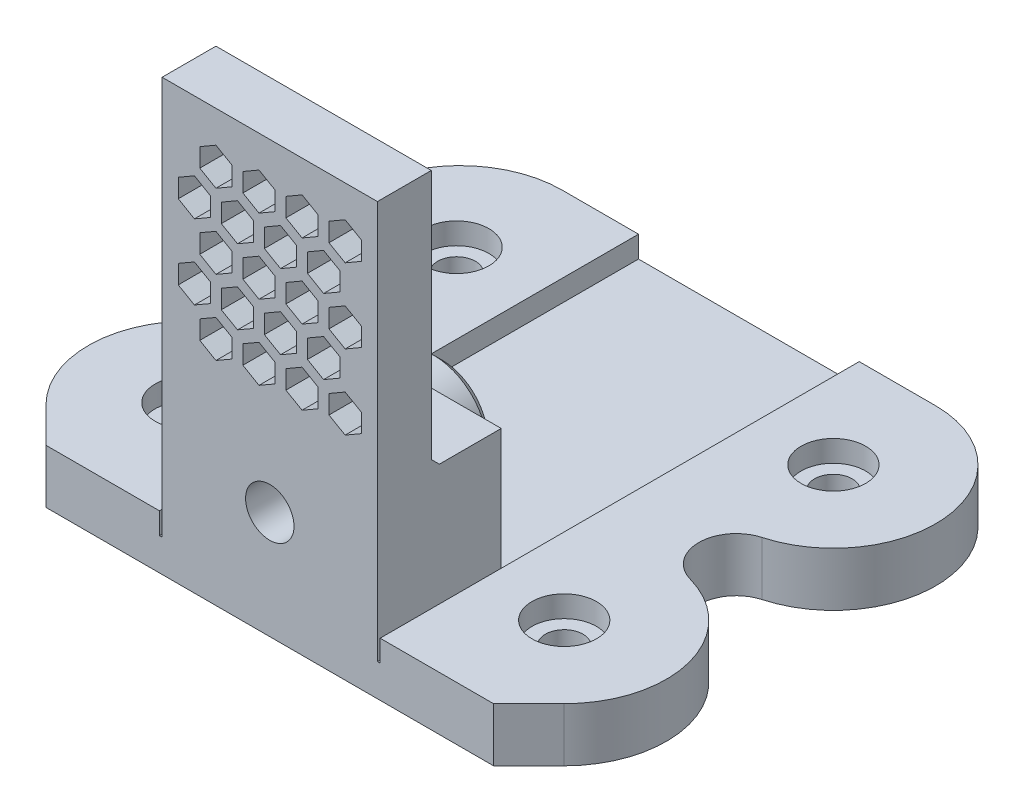
SolidWorks part; units mm, degrees
ref_plane "Front Plane" through (0, 0, 0) normal (0, 0, 1) x (1, 0, 0)
ref_plane "Top Plane" through (0, 0, 0) normal (0, 1, 0) x (1, 0, 0)
ref_plane "Right Plane" through (0, 0, 0) normal (1, 0, 0) x (0, 0, -1)
sketch "Sketch1" plane through (0, 0, 0) normal (1, 0, 0) x (0, 0, -1)
  line L0 (0, 0) -> (0, 40)
  line L1 (0, 40) -> (5, 40)
  line L2 (5, 40) -> (5, 16.75)
  line L3 (5, 16.75) -> (5.75, 16)
  line L4 (5.75, 16) -> (11.5, 16)
  line L5 (11.5, 16) -> (11.5, 3)
  line L6 (11.5, 3) -> (44.5, 3)
  line L7 (44.5, 3) -> (44.5, 0)
  line L8 (44.5, 0) -> (0, 0)
  line L9 (11.5, 3) -> (44, 3) construction
  line L10 (11.5, 16) -> (11.5, 3) construction
  line L11 (7, 16) -> (11.5, 16) construction
  dimension "D1" = 40
  dimension "D2" = 6.5
  dimension "D3" = 135
  dimension "D4" = 0.75
  dimension "D5" = 33
extrude "Boss-Extrude1" add sketch "Sketch1" against normal blind 20
sketch "Sketch2" plane through (0, 0, -11.5) normal (0, 0, -1) x (-1, 0, 0)
  circle A0 centre (10, 10) radius 2 construction
  circle A1 centre (10, 10) radius 5.25 construction
  circle A2 centre (10, 10) radius 5
  circle A3 centre (10, 10) radius 2.25
  circle A4 centre (10, 10) radius 2.75 construction
  dimension "D3" = 4
  dimension "D4" = 10
  dimension "D1" = 0.25
  dimension "D2" = 0.25
extrude "Boss-Extrude2" add sketch "Sketch2" along normal blind 4.5
chamfer "Chamfer1" distance 0.75 angle 45 1 edges at (-10, 15, -16)
extrude "Cut-Extrude1" cut sketch "Sketch2<2>" against normal up to next contours A3 region at (-10, 10, -11.5)
sketch "Sketch2<2>" plane through (0, 0, -11.5) normal (0, 0, -1) x (-1, 0, 0) same geometry as "Sketch2"
sketch "Sketch3" plane through (0, 3, 0) normal (0, 1, 0) x (1, 0, 0)
  line L0 (0, 44.5) -> (7.35, 44.5)
  line L1 (-10, 44.5) -> (-10, 11.5) construction
  line L2 (-20, 44.5) -> (0, 44.5) construction
  line L3 (-20, 11.5) -> (0, 11.5) construction
  line L4 (7.35, 44.5) -> (7.35, 0.5) construction
  line L5 (14.0675, 3.2825) -> (10.785, 0)
  line L6 (10.785, 0) -> (0, 0)
  line L7 (0, 0) -> (0, 11.5)
  line L8 (0, 11.5) -> (-20, 11.5)
  line L9 (0, 44.5) -> (-20, 44.5)
  line L10 (-20, 0) -> (-20, 11.5)
  line L11 (-30.785, 0) -> (-20, 0)
  line L12 (-34.0675, 3.2825) -> (-30.785, 0)
  line L13 (-20, 44.5) -> (-27.35, 44.5)
  arc A0 (7.35, 44.5) -> (9.8936, 25.8469) centre (7.35, 35) cw
  arc A1 (9.8936, 25.8469) -> (9.8936, 19.1531) centre (10.8237, 22.5) ccw
  arc A2 (9.8936, 19.1531) -> (14.0675, 3.2825) centre (7.35, 10) cw
  circle A3 centre (7.35, 35) radius 1.75 construction
  circle A4 centre (7.35, 10) radius 1.75
  circle A5 centre (7.35, 10) radius 1.75 construction
  arc A6 (14.0675, 3.2825) -> (7.35, 0.5) centre (7.35, 10) cw construction
  circle A7 centre (7.35, 35) radius 1.75
  arc A10 (-29.8936, 19.1531) -> (-34.0675, 3.2825) centre (-27.35, 10) ccw
  arc A11 (-29.8936, 25.8469) -> (-29.8936, 19.1531) centre (-30.8237, 22.5) cw
  arc A12 (-27.35, 44.5) -> (-29.8936, 25.8469) centre (-27.35, 35) ccw
  circle A14 centre (-27.65, 10) radius 1.75
  circle A15 centre (-27.65, 35) radius 1.75
  circle A16 centre (-27.65, 35) radius 1.75 construction
  circle A17 centre (-27.65, 10) radius 1.75 construction
  point P22 (7.35, 22.5)
  point P37 (-27.35, 22.5)
  dimension "D2" = 3.5
  dimension "D1" = 135
extrude "Boss-Extrude3" add sketch "Sketch3" against normal up to surface (3 mm away) up to face at (-10, 0, -22.25)
sketch "Sketch4" plane through (0, 3, 0) normal (0, 1, 0) x (1, 0, 0)
  line L0 (-30.785, 0) -> (-20, 0) construction
  line L1 (-34.0675, 3.2825) -> (-30.785, 0) construction
  line L2 (-27.35, 44.5) -> (7.35, 44.5) construction
  line L3 (10.785, 0) -> (14.0675, 3.2825) construction
  line L5 (-30.785, 0) -> (-20.25, 0)
  line L6 (-34.0675, 3.2825) -> (-30.785, 0)
  line L7 (-27.35, 44.5) -> (-20.25, 44.5)
  line L8 (10.785, 0) -> (14.0675, 3.2825)
  line L10 (-20, 0) -> (-20, 11.5) construction
  line L11 (0, 11.5) -> (0, 0) construction
  line L20 (-20, 0) -> (-20, 11.5) construction
  line L21 (0, 11.5) -> (0, 0) construction
  line L22 (0.25, 44.5) -> (0.25, 0)
  line L23 (0.25, 11.5) -> (0.25, 0) construction
  line L24 (-20.25, 0) -> (-20.25, 44.5)
  line L25 (-20.25, 0) -> (-20.25, 11.5) construction
  line L26 (0.25, 44.5) -> (7.35, 44.5)
  line L27 (-20.25, 44.5) -> (0.25, 44.5) construction
  line L28 (0.25, 0) -> (10.785, 0)
  arc A0 (-29.8936, 19.1531) -> (-34.0675, 3.2825) centre (-27.35, 10) ccw construction
  arc A1 (-29.8936, 19.1531) -> (-29.8936, 25.8469) centre (-30.8237, 22.5) ccw construction
  arc A2 (-27.35, 44.5) -> (-29.8936, 25.8469) centre (-27.35, 35) ccw construction
  arc A3 (9.8936, 25.8469) -> (7.35, 44.5) centre (7.35, 35) ccw construction
  arc A4 (9.8936, 25.8469) -> (9.8936, 19.1531) centre (10.8237, 22.5) ccw construction
  arc A5 (14.0675, 3.2825) -> (9.8936, 19.1531) centre (7.35, 10) ccw construction
  arc A6 (-29.8936, 19.1531) -> (-34.0675, 3.2825) centre (-27.35, 10) ccw
  arc A7 (-29.8936, 19.1531) -> (-29.8936, 25.8469) centre (-30.8237, 22.5) ccw
  arc A8 (-27.35, 44.5) -> (-29.8936, 25.8469) centre (-27.35, 35) ccw
  arc A9 (9.8936, 25.8469) -> (7.35, 44.5) centre (7.35, 35) ccw
  arc A10 (9.8936, 25.8469) -> (9.8936, 19.1531) centre (10.8237, 22.5) ccw
  arc A11 (14.0675, 3.2825) -> (9.8936, 19.1531) centre (7.35, 10) ccw
  circle A12 centre (7.35, 10) radius 2.75 construction
  circle A13 centre (7.35, 35) radius 3
  circle A16 centre (7.35, 10) radius 3
  circle A19 centre (-27.65, 10) radius 3
  circle A20 centre (-27.65, 35) radius 3
  circle A21 centre (-27.65, 35) radius 1.75 construction
  circle A22 centre (-27.65, 10) radius 1.75 construction
  dimension "D1" = 0.25
  dimension "D2" = 0.25
  dimension "D4" = 5.5
  dimension "D3" = 0.25
extrude "Boss-Extrude4" add sketch "Sketch4" along normal blind 2
sketch "Sketch5" plane through (0, 0, -5) normal (0, 0, -1) x (-1, 0, 0)
  line L0 (1.5, 37.0353) -> (0, 37.0353) construction
  line L1 (3, 19.7147) -> (4.5, 20.5808)
  line L2 (4.5, 20.5808) -> (4.5, 22.3128)
  line L3 (4.5, 22.3128) -> (3, 23.1788)
  line L4 (3, 23.1788) -> (1.5, 22.3128)
  line L5 (1.5, 22.3128) -> (1.5, 20.5808)
  line L6 (1.5, 20.5808) -> (3, 19.7147)
  line L7 (1.5, 19.7147) -> (18.5, 19.7147) construction
  line L8 (1.5, 19.7147) -> (1.5, 37.0353) construction
  line L9 (1.5, 37.0353) -> (18.5, 37.0353) construction
  line L10 (18.5, 19.7147) -> (18.5, 37.0353) construction
  line L11 (0, 16.75) -> (0, 40) construction
  line L12 (1.5, 40) -> (1.5, 37.0353) construction
  line L13 (20, 40) -> (0, 40) construction
  line L14 (20, 19.7147) -> (18.5, 19.7147) construction
  line L15 (20, 16.75) -> (20, 40) construction
  line L16 (18.5, 19.7147) -> (18.5, 16.75) construction
  line L17 (20, 16.75) -> (0, 16.75) construction
  line L18 (7, 19.7147) -> (8.5, 20.5808)
  line L19 (8.5, 20.5808) -> (8.5, 22.3128)
  line L20 (8.5, 22.3128) -> (7, 23.1788)
  line L21 (7, 23.1788) -> (5.5, 22.3128)
  line L22 (5.5, 22.3128) -> (5.5, 20.5808)
  line L23 (5.5, 20.5808) -> (7, 19.7147)
  line L24 (11, 19.7147) -> (12.5, 20.5808)
  line L25 (12.5, 20.5808) -> (12.5, 22.3128)
  line L26 (12.5, 22.3128) -> (11, 23.1788)
  line L27 (11, 23.1788) -> (9.5, 22.3128)
  line L28 (9.5, 22.3128) -> (9.5, 20.5808)
  line L29 (9.5, 20.5808) -> (11, 19.7147)
  line L30 (15, 19.7147) -> (16.5, 20.5808)
  line L31 (16.5, 20.5808) -> (16.5, 22.3128)
  line L32 (16.5, 22.3128) -> (15, 23.1788)
  line L33 (15, 23.1788) -> (13.5, 22.3128)
  line L34 (13.5, 22.3128) -> (13.5, 20.5808)
  line L35 (13.5, 20.5808) -> (15, 19.7147)
  line L36 (19, 19.7147) -> (20.5, 20.5808) construction
  line L37 (20.5, 20.5808) -> (20.5, 22.3128) construction
  line L38 (20.5, 22.3128) -> (19, 23.1788) construction
  line L39 (19, 23.1788) -> (17.5, 22.3128) construction
  line L40 (17.5, 22.3128) -> (17.5, 20.5808) construction
  line L41 (17.5, 20.5808) -> (19, 19.7147) construction
  line L42 (23, 19.7147) -> (24.5, 20.5808) construction
  line L43 (24.5, 20.5808) -> (24.5, 22.3128) construction
  line L44 (24.5, 22.3128) -> (23, 23.1788) construction
  line L45 (23, 23.1788) -> (21.5, 22.3128) construction
  line L46 (21.5, 22.3128) -> (21.5, 20.5808) construction
  line L47 (21.5, 20.5808) -> (23, 19.7147) construction
  line L60 (3, 21.4468) -> (-6, 37.0353) construction
  line L61 (-6, 37.0353) -> (0, 37.0353) construction
  line L68 (5, 23.1788) -> (6.5, 24.0449)
  line L69 (6.5, 24.0449) -> (6.5, 25.7769)
  line L70 (6.5, 25.7769) -> (5, 26.6429)
  line L71 (5, 26.6429) -> (3.5, 25.7769)
  line L72 (3.5, 25.7769) -> (3.5, 24.0449)
  line L73 (3.5, 24.0449) -> (5, 23.1788)
  line L74 (9, 23.1788) -> (10.5, 24.0449)
  line L75 (10.5, 24.0449) -> (10.5, 25.7769)
  line L76 (10.5, 25.7769) -> (9, 26.6429)
  line L77 (9, 26.6429) -> (7.5, 25.7769)
  line L78 (7.5, 25.7769) -> (7.5, 24.0449)
  line L79 (7.5, 24.0449) -> (9, 23.1788)
  line L80 (13, 23.1788) -> (14.5, 24.0449)
  line L81 (14.5, 24.0449) -> (14.5, 25.7769)
  line L82 (14.5, 25.7769) -> (13, 26.6429)
  line L83 (13, 26.6429) -> (11.5, 25.7769)
  line L84 (11.5, 25.7769) -> (11.5, 24.0449)
  line L85 (11.5, 24.0449) -> (13, 23.1788)
  line L86 (17, 23.1788) -> (18.5, 24.0449)
  line L87 (18.5, 24.0449) -> (18.5, 25.7769)
  line L88 (18.5, 25.7769) -> (17, 26.6429)
  line L89 (17, 26.6429) -> (15.5, 25.7769)
  line L90 (15.5, 25.7769) -> (15.5, 24.0449)
  line L91 (15.5, 24.0449) -> (17, 23.1788)
  line L116 (3, 26.6429) -> (4.5, 27.509)
  line L117 (4.5, 27.509) -> (4.5, 29.241)
  line L118 (4.5, 29.241) -> (3, 30.1071)
  line L119 (3, 30.1071) -> (1.5, 29.241)
  line L120 (1.5, 29.241) -> (1.5, 27.509)
  line L121 (1.5, 27.509) -> (3, 26.6429)
  line L122 (7, 26.6429) -> (8.5, 27.509)
  line L123 (8.5, 27.509) -> (8.5, 29.241)
  line L124 (8.5, 29.241) -> (7, 30.1071)
  line L125 (7, 30.1071) -> (5.5, 29.241)
  line L126 (5.5, 29.241) -> (5.5, 27.509)
  line L127 (5.5, 27.509) -> (7, 26.6429)
  line L128 (11, 26.6429) -> (12.5, 27.509)
  line L129 (12.5, 27.509) -> (12.5, 29.241)
  line L130 (12.5, 29.241) -> (11, 30.1071)
  line L131 (11, 30.1071) -> (9.5, 29.241)
  line L132 (9.5, 29.241) -> (9.5, 27.509)
  line L133 (9.5, 27.509) -> (11, 26.6429)
  line L134 (15, 26.6429) -> (16.5, 27.509)
  line L135 (16.5, 27.509) -> (16.5, 29.241)
  line L136 (16.5, 29.241) -> (15, 30.1071)
  line L137 (15, 30.1071) -> (13.5, 29.241)
  line L138 (13.5, 29.241) -> (13.5, 27.509)
  line L139 (13.5, 27.509) -> (15, 26.6429)
  line L170 (5, 30.1071) -> (6.5, 30.9731)
  line L171 (6.5, 30.9731) -> (6.5, 32.7051)
  line L172 (6.5, 32.7051) -> (5, 33.5712)
  line L173 (5, 33.5712) -> (3.5, 32.7051)
  line L174 (3.5, 32.7051) -> (3.5, 30.9731)
  line L175 (3.5, 30.9731) -> (5, 30.1071)
  line L176 (9, 30.1071) -> (10.5, 30.9731)
  line L177 (10.5, 30.9731) -> (10.5, 32.7051)
  line L178 (10.5, 32.7051) -> (9, 33.5712)
  line L179 (9, 33.5712) -> (7.5, 32.7051)
  line L180 (7.5, 32.7051) -> (7.5, 30.9731)
  line L181 (7.5, 30.9731) -> (9, 30.1071)
  line L182 (13, 30.1071) -> (14.5, 30.9731)
  line L183 (14.5, 30.9731) -> (14.5, 32.7051)
  line L184 (14.5, 32.7051) -> (13, 33.5712)
  line L185 (13, 33.5712) -> (11.5, 32.7051)
  line L186 (11.5, 32.7051) -> (11.5, 30.9731)
  line L187 (11.5, 30.9731) -> (13, 30.1071)
  line L188 (17, 30.1071) -> (18.5, 30.9731)
  line L189 (18.5, 30.9731) -> (18.5, 32.7051)
  line L190 (18.5, 32.7051) -> (17, 33.5712)
  line L191 (17, 33.5712) -> (15.5, 32.7051)
  line L192 (15.5, 32.7051) -> (15.5, 30.9731)
  line L193 (15.5, 30.9731) -> (17, 30.1071)
  line L218 (3, 33.5712) -> (4.5, 34.4372)
  line L219 (4.5, 34.4372) -> (4.5, 36.1692)
  line L220 (4.5, 36.1692) -> (3, 37.0353)
  line L221 (3, 37.0353) -> (1.5, 36.1692)
  line L222 (1.5, 36.1692) -> (1.5, 34.4372)
  line L223 (1.5, 34.4372) -> (3, 33.5712)
  line L224 (7, 33.5712) -> (8.5, 34.4372)
  line L225 (8.5, 34.4372) -> (8.5, 36.1692)
  line L226 (8.5, 36.1692) -> (7, 37.0353)
  line L227 (7, 37.0353) -> (5.5, 36.1692)
  line L228 (5.5, 36.1692) -> (5.5, 34.4372)
  line L229 (5.5, 34.4372) -> (7, 33.5712)
  line L230 (11, 33.5712) -> (12.5, 34.4372)
  line L231 (12.5, 34.4372) -> (12.5, 36.1692)
  line L232 (12.5, 36.1692) -> (11, 37.0353)
  line L233 (11, 37.0353) -> (9.5, 36.1692)
  line L234 (9.5, 36.1692) -> (9.5, 34.4372)
  line L235 (9.5, 34.4372) -> (11, 33.5712)
  line L236 (15, 33.5712) -> (16.5, 34.4372)
  line L237 (16.5, 34.4372) -> (16.5, 36.1692)
  line L238 (16.5, 36.1692) -> (15, 37.0353)
  line L239 (15, 37.0353) -> (13.5, 36.1692)
  line L240 (13.5, 36.1692) -> (13.5, 34.4372)
  line L241 (13.5, 34.4372) -> (15, 33.5712)
  line L302 (1, 23.1788) -> (2.5, 24.0449) [skipped]
  line L303 (2.5, 24.0449) -> (2.5, 25.7769) [skipped]
  line L304 (2.5, 25.7769) -> (1, 26.6429) [skipped]
  line L305 (1, 26.6429) -> (-0.5, 25.7769) [skipped]
  line L306 (-0.5, 25.7769) -> (-0.5, 24.0449) [skipped]
  line L307 (-0.5, 24.0449) -> (1, 23.1788) [skipped]
  line L308 (1, 30.1071) -> (2.5, 30.9731) [skipped]
  line L309 (2.5, 30.9731) -> (2.5, 32.7051) [skipped]
  line L310 (2.5, 32.7051) -> (1, 33.5712) [skipped]
  line L311 (1, 33.5712) -> (-0.5, 32.7051) [skipped]
  line L312 (-0.5, 32.7051) -> (-0.5, 30.9731) [skipped]
  line L313 (-0.5, 30.9731) -> (1, 30.1071) [skipped]
  line L314 (1, 37.0353) -> (2.5, 37.9013) [skipped]
  line L315 (2.5, 37.9013) -> (2.5, 39.6333) [skipped]
  line L316 (2.5, 39.6333) -> (1, 40.4994) [skipped]
  line L317 (1, 40.4994) -> (-0.5, 39.6333) [skipped]
  line L318 (-0.5, 39.6333) -> (-0.5, 37.9013) [skipped]
  line L319 (-0.5, 37.9013) -> (1, 37.0353) [skipped]
  line L320 (-1, 33.5712) -> (0.5, 34.4372) [skipped]
  line L321 (0.5, 34.4372) -> (0.5, 36.1692) [skipped]
  line L322 (0.5, 36.1692) -> (-1, 37.0353) [skipped]
  line L323 (-1, 37.0353) -> (-2.5, 36.1692) [skipped]
  line L324 (-2.5, 36.1692) -> (-2.5, 34.4372) [skipped]
  line L325 (-2.5, 34.4372) -> (-1, 33.5712) [skipped]
  line L326 (-3, 37.0353) -> (-1.5, 37.9013) [skipped]
  line L327 (-1.5, 37.9013) -> (-1.5, 39.6333) [skipped]
  line L328 (-1.5, 39.6333) -> (-3, 40.4994) [skipped]
  line L329 (-3, 40.4994) -> (-4.5, 39.6333) [skipped]
  line L330 (-4.5, 39.6333) -> (-4.5, 37.9013) [skipped]
  line L331 (-4.5, 37.9013) -> (-3, 37.0353) [skipped]
  line L332 (-7, 37.0353) -> (-5.5, 37.9013) [skipped]
  line L333 (-5.5, 37.9013) -> (-5.5, 39.6333) [skipped]
  line L334 (-5.5, 39.6333) -> (-7, 40.4994) [skipped]
  line L335 (-7, 40.4994) -> (-8.5, 39.6333) [skipped]
  line L336 (-8.5, 39.6333) -> (-8.5, 37.9013) [skipped]
  line L337 (-8.5, 37.9013) -> (-7, 37.0353) [skipped]
  line L338 (-5, 33.5712) -> (-3.5, 34.4372) [skipped]
  line L339 (-3.5, 34.4372) -> (-3.5, 36.1692) [skipped]
  line L340 (-3.5, 36.1692) -> (-5, 37.0353) [skipped]
  line L341 (-5, 37.0353) -> (-6.5, 36.1692) [skipped]
  line L342 (-6.5, 36.1692) -> (-6.5, 34.4372) [skipped]
  line L343 (-6.5, 34.4372) -> (-5, 33.5712) [skipped]
  line L344 (-3, 30.1071) -> (-1.5, 30.9731) [skipped]
  line L345 (-1.5, 30.9731) -> (-1.5, 32.7051) [skipped]
  line L346 (-1.5, 32.7051) -> (-3, 33.5712) [skipped]
  line L347 (-3, 33.5712) -> (-4.5, 32.7051) [skipped]
  line L348 (-4.5, 32.7051) -> (-4.5, 30.9731) [skipped]
  line L349 (-4.5, 30.9731) -> (-3, 30.1071) [skipped]
  line L350 (-1, 26.6429) -> (0.5, 27.509) [skipped]
  line L351 (0.5, 27.509) -> (0.5, 29.241) [skipped]
  line L352 (0.5, 29.241) -> (-1, 30.1071) [skipped]
  line L353 (-1, 30.1071) -> (-2.5, 29.241) [skipped]
  line L354 (-2.5, 29.241) -> (-2.5, 27.509) [skipped]
  line L355 (-2.5, 27.509) -> (-1, 26.6429) [skipped]
  line L356 (31, 19.7147) -> (32.5, 20.5808) [skipped]
  line L357 (32.5, 20.5808) -> (32.5, 22.3128) [skipped]
  line L358 (32.5, 22.3128) -> (31, 23.1788) [skipped]
  line L359 (31, 23.1788) -> (29.5, 22.3128) [skipped]
  line L360 (29.5, 22.3128) -> (29.5, 20.5808) [skipped]
  line L361 (29.5, 20.5808) -> (31, 19.7147) [skipped]
  line L380 (19, 26.6429) -> (20.5, 27.509) [skipped]
  line L381 (20.5, 27.509) -> (20.5, 29.241) [skipped]
  line L382 (20.5, 29.241) -> (19, 30.1071) [skipped]
  line L383 (19, 30.1071) -> (17.5, 29.241) [skipped]
  line L384 (17.5, 29.241) -> (17.5, 27.509) [skipped]
  line L385 (17.5, 27.509) -> (19, 26.6429) [skipped]
  line L386 (21, 23.1788) -> (22.5, 24.0449) [skipped]
  line L387 (22.5, 24.0449) -> (22.5, 25.7769) [skipped]
  line L388 (22.5, 25.7769) -> (21, 26.6429) [skipped]
  line L389 (21, 26.6429) -> (19.5, 25.7769) [skipped]
  line L390 (19.5, 25.7769) -> (19.5, 24.0449) [skipped]
  line L391 (19.5, 24.0449) -> (21, 23.1788) [skipped]
  line L404 (13, 37.0353) -> (14.5, 37.9013) [skipped]
  line L405 (14.5, 37.9013) -> (14.5, 39.6333) [skipped]
  line L406 (14.5, 39.6333) -> (13, 40.4994) [skipped]
  line L407 (13, 40.4994) -> (11.5, 39.6333) [skipped]
  line L408 (11.5, 39.6333) -> (11.5, 37.9013) [skipped]
  line L409 (11.5, 37.9013) -> (13, 37.0353) [skipped]
  line L410 (9, 37.0353) -> (10.5, 37.9013) [skipped]
  line L411 (10.5, 37.9013) -> (10.5, 39.6333) [skipped]
  line L412 (10.5, 39.6333) -> (9, 40.4994) [skipped]
  line L413 (9, 40.4994) -> (7.5, 39.6333) [skipped]
  line L414 (7.5, 39.6333) -> (7.5, 37.9013) [skipped]
  line L415 (7.5, 37.9013) -> (9, 37.0353) [skipped]
  line L416 (5, 37.0353) -> (6.5, 37.9013) [skipped]
  line L417 (6.5, 37.9013) -> (6.5, 39.6333) [skipped]
  line L418 (6.5, 39.6333) -> (5, 40.4994) [skipped]
  line L419 (5, 40.4994) -> (3.5, 39.6333) [skipped]
  line L420 (3.5, 39.6333) -> (3.5, 37.9013) [skipped]
  line L421 (3.5, 37.9013) -> (5, 37.0353) [skipped]
  line L422 (27, 19.7147) -> (28.5, 20.5808) construction
  line L423 (28.5, 20.5808) -> (28.5, 22.3128) construction
  line L424 (28.5, 22.3128) -> (27, 23.1788) construction
  line L425 (27, 23.1788) -> (25.5, 22.3128) construction
  line L426 (25.5, 22.3128) -> (25.5, 20.5808) construction
  line L427 (25.5, 20.5808) -> (27, 19.7147) construction
  circle A0 centre (3, 21.4468) radius 1.5 construction
  dimension "D1" = 3
  dimension "D2" = 1.5
  dimension "D4" = 1
  dimension "D6" = 1
  dimension "D3" = 8
  dimension "D5" = 6
extrude "Cut-Extrude2" cut sketch "Sketch5" against normal up to next
equation "\"Tolerance\" = 0.25mm"
equation "\"Pocket_Head_M5\"= 8mm"
equation "\"Pocket_Head_M4\" = 7mm"
equation "\"Pocket_Nut_M4\" = 7mm"
equation "\"Pocket_Nut_M5\"= 8mm"
equation "\"Pocket_Nut_M3\"= 5.5mm"
equation "\"Pocket_Head_M3\"= 5.5mm"
equation "\"D1@Sketch2\"=\"Tolerance\""
equation "\"D2@Sketch2\"=\"Tolerance\""
equation "\"D1@Sketch4\"=\"Tolerance\""
equation "\"D2@Sketch4\"=\"Tolerance\""
equation "\"D3@Sketch4\"=\"Tolerance\""
equation "\"D4@Sketch4\"=\"Pocket_Head_M3\""
